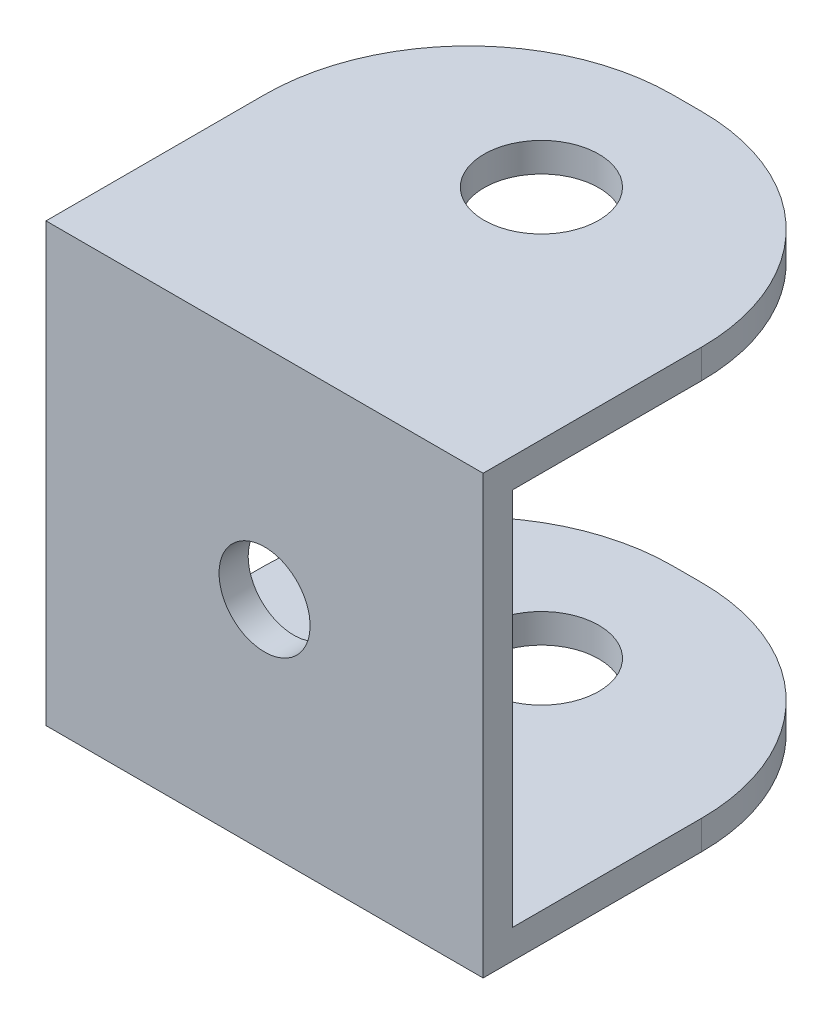
SolidWorks part; units mm, degrees
ref_plane "Front Plane" through (0, 0, 0) normal (0, 0, 1) x (1, 0, 0)
ref_plane "Top Plane" through (0, 0, 0) normal (0, 1, 0) x (1, 0, 0)
ref_plane "Right Plane" through (0, 0, 0) normal (1, 0, 0) x (0, 0, -1)
sketch "Sketch2" plane through (0, 0, 0) normal (0, 0, 1) x (1, 0, 0)
  line L1 (0, 0) -> (38.1, 0)
  line L2 (0, 0) -> (0, 38.1)
  line L3 (0, 38.1) -> (38.1, 38.1)
  line L4 (38.1, 0) -> (38.1, 38.1)
  dimension "D1" = 38.1
  dimension "D2" = 38.1
extrude "Boss-Extrude1" add sketch "Sketch2" along normal blind 2.54
hole_wizard "5/16 (0.3125) Diameter Hole1" positions "3DSketch1" profile "Sketch3" hole size "5/16" standard "ANSI Inch" end condition through all
sketch3d "3DSketch1"
  line L0 (38.1, 38.1, 0) -> (0, 38.1, 0) construction
  line L1 (0, 38.1, 0) -> (0, 0, 0) construction
  point P0 (19.05, 19.05, 0)
  dimension "D1" = 19.05
  dimension "D2" = 19.05
sketch "Sketch3" plane through (19.05, 19.05, 0) normal (1, 0, 0) x (0, 1, 0)
  line L0 (0, 0) -> (0, 2.54)
  line L1 (0, 2.54) -> (3.9687, 2.54)
  line L2 (3.9687, 2.54) -> (3.9687, 0)
  line L5 (3.9687, 0) -> (0, 0)
  line L11 (0, -6.35) -> (0, 107.95) construction
  dimension "Thru Hole Dia." = 7.9375
  dimension "Thru Hole Depth" = 2.54
sketch "Sketch4" plane through (0, 38.1, 0) normal (0, 1, 0) x (1, 0, 0)
  line L0 (0, 0) -> (0, 16.51)
  line L1 (38.1, 0) -> (38.1, 16.51)
  line L2 (20.32, 34.29) -> (17.78, 34.29)
  line L7 (38.1, 0) -> (0, 0)
  line L8 (0, 0) -> (0, -2.54)
  line L9 (0, -2.54) -> (38.1, -2.54)
  line L10 (38.1, -2.54) -> (38.1, 0)
  line L12 (0, 0) -> (0, -2.54)
  line L13 (0, -2.54) -> (38.1, -2.54)
  line L14 (38.1, -2.54) -> (38.1, 0)
  arc A0 (0, 16.51) -> (17.78, 34.29) centre (17.78, 16.51) cw
  arc A1 (38.1, 16.51) -> (20.32, 34.29) centre (20.32, 16.51) ccw
  point P8 (0, 34.29)
  dimension "D2" = 17.78
  dimension "D3" = 17.78
  dimension "D1" = 34.29
  dimension "D4" = 0
extrude "Boss-Extrude2" add sketch "Sketch4" against normal blind 2.54
sketch "Sketch7" plane through (0, 38.1, 0) normal (0, 1, 0) x (1, 0, 0)
  line L0 (38.1, -2.54) -> (38.1, 16.51) construction
  line L1 (20.32, 34.29) -> (17.78, 34.29) construction
  point P0 (19.05, 21.59)
  dimension "D1" = 19.05
  dimension "D2" = 12.7
hole_wizard "Ø10.0mm Dowel Hole1" positions "Sketch7" profile "Sketch8" hole size "Ø10.0" standard "ANSI Metric" end condition through all
sketch "Sketch8" plane through (19.05, 38.1, -21.59) normal (1, 0, 0) x (0, 0, 1)
  line L0 (0, 0) -> (0, 38.1)
  line L1 (0, 38.1) -> (5, 38.1)
  line L2 (5, 38.1) -> (5, 0)
  line L5 (5, 0) -> (0, 0)
  line L11 (0, -6.35) -> (0, 107.95) construction
  dimension "Thru Hole Dia." = 10
  dimension "Thru Hole Depth" = 38.1
ref_axis "Axis1" through (19.05, 19.05, 0) along (0, 0, 1)
ref_plane "Plane1" through (0, 19.05, 0) normal (0, -1, 0) x (-1, 0, 0)
mirror "Mirror4" about plane through (0, 19.05, 0) normal (0, -1, 0) of "Ø10.0mm Dowel Hole1", "5/16 (0.3125) Diameter Hole1", "Boss-Extrude1", "Boss-Extrude2"
